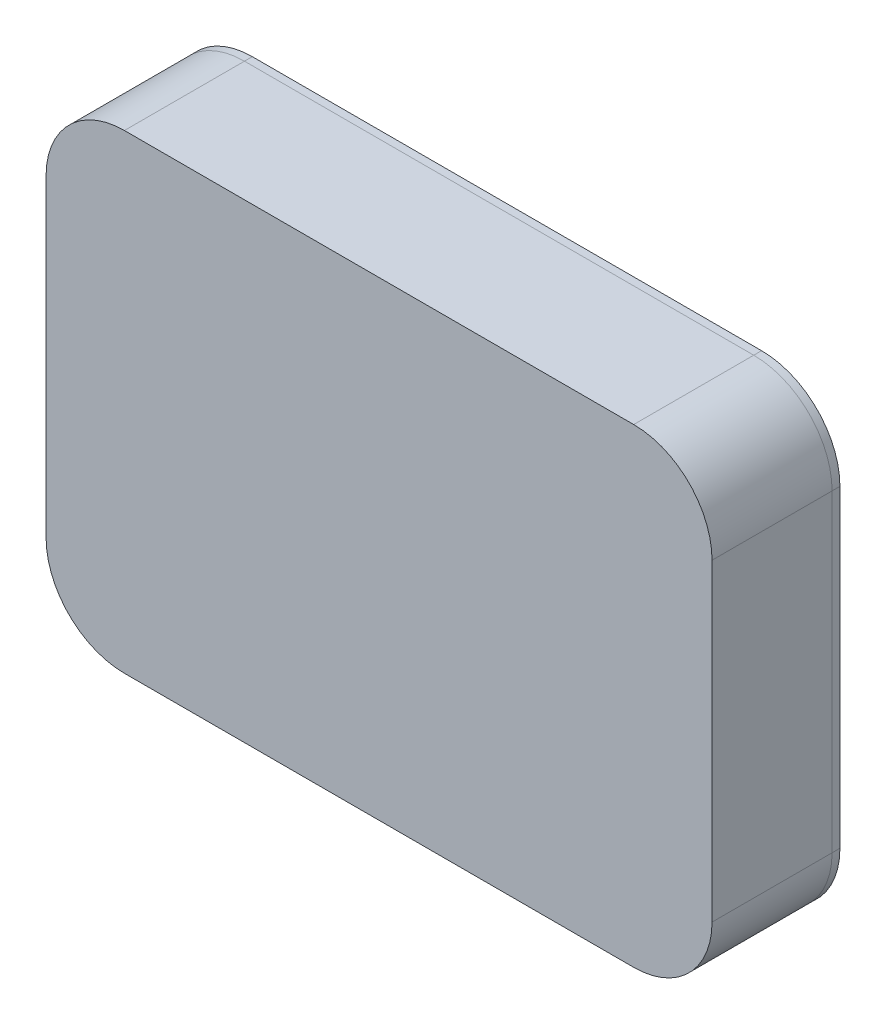
SolidWorks part; units mm, degrees
ref_plane "Plan de face" through (0, 0, 0) normal (0, 0, 1) x (1, 0, 0)
ref_plane "Plan de dessus" through (0, 0, 0) normal (0, 1, 0) x (1, 0, 0)
ref_plane "Plan de droite" through (0, 0, 0) normal (1, 0, 0) x (0, 0, -1)
sketch "Esquisse1" plane through (0, 0, 0) normal (0, 0, 1) x (1, 0, 0)
  line L1 (-32.5, 30) -> (32.5, 30)
  line L2 (-42.5, 20) -> (-42.5, -20)
  line L3 (-32.5, -30) -> (32.5, -30)
  line L4 (42.5, 20) -> (42.5, -20)
  line L5 (-42.5, 30) -> (42.5, -30) construction
  line L6 (-42.5, -30) -> (42.5, 30) construction
  arc A0 (-42.5, -20) -> (-32.5, -30) centre (-32.5, -20) ccw
  arc A1 (32.5, -30) -> (42.5, -20) centre (32.5, -20) ccw
  arc A2 (32.5, 30) -> (42.5, 20) centre (32.5, 20) cw
  arc A3 (-32.5, 30) -> (-42.5, 20) centre (-32.5, 20) ccw
  point P0 (0, 0)
  dimension "D1" = 10
  dimension "D2" = 40
  dimension "D3" = 65
sketch "profil" plane through (0, 0, 0) normal (1, 0, 0) x (0, 0, -1)
  line L0 (0, -28.4) -> (5.2972, -28.4)
  line L1 (5.2972, -28.4) -> (14.1228, -23.8)
  line L3 (14.1228, -30) -> (0, -30)
  line L4 (0, -30) -> (0, -28.4)
  line L6 (0, -20) -> (0, -30) construction
  line L7 (0, -30) -> (0, 30) construction
  line L8 (14.1228, -23.8) -> (14.1228, -25.4) construction
  line L9 (14.1228, -28.4) -> (14.1228, -30) construction
  line L10 (14.1228, -23.8) -> (15.1228, -23.8)
  line L11 (15.1228, -23.8) -> (15.1228, -25.4)
  line L12 (15.1228, -25.4) -> (14.1228, -25.4)
  line L13 (14.1228, -30) -> (15.1228, -30)
  line L14 (15.1228, -30) -> (15.1228, -28.4)
  line L15 (15.1228, -28.4) -> (14.1228, -28.4)
  arc A0 (14.1228, -25.4) -> (14.1228, -28.4) centre (14.1228, -26.9) ccw
  dimension "D1" = 3
  dimension "D3" = 14.1228
  dimension "D4" = 1
sweep "Balayage1" add profiles "profil" path "Esquisse1"
extrude "Boss.-Extru.1" add sketch "Esquisse1<3>" along normal blind 1.2
sketch "Esquisse1<3>" plane through (0, 0, 0) normal (0, 0, 1) x (1, 0, 0) same geometry as "Esquisse1"
fillet "Congé1" radius 2 9 edges at (-38.4397, 25.9397, 0) (-40.9, 0, 0) (-38.4397, -25.9397, 0) (-16.25, -28.4, 0) (16.25, -28.4, 0) (38.4397, -25.9397, 0) (40.9, 0, 0) (38.4397, 25.9397, 0) (0, 28.4, 0)
equation "\"buse\"=0.4"
equation "\"coque\"= \"buse\" * 4"
equation "\"diam_silicone\"=3"
equation "\"D1@profil\" = \"diam_silicone\""
equation "\"couche\"=0.2"
equation "\"D1@Boss.-Extru.1\"=\"fond\""
equation "\"fond\"= \"couche\" * 6"
equation "\"dim_ext\" = 40"
equation "\"D2@Esquisse1\"=\"dim_ext\""
equation "\"dim_ext_L\"= 65"
equation "\"D3@Esquisse1\"=\"dim_ext_L\""
equation "\"hauteur_boitier\"=14.1228"
equation "\"D3@profil\"=\"hauteur_boitier\""
